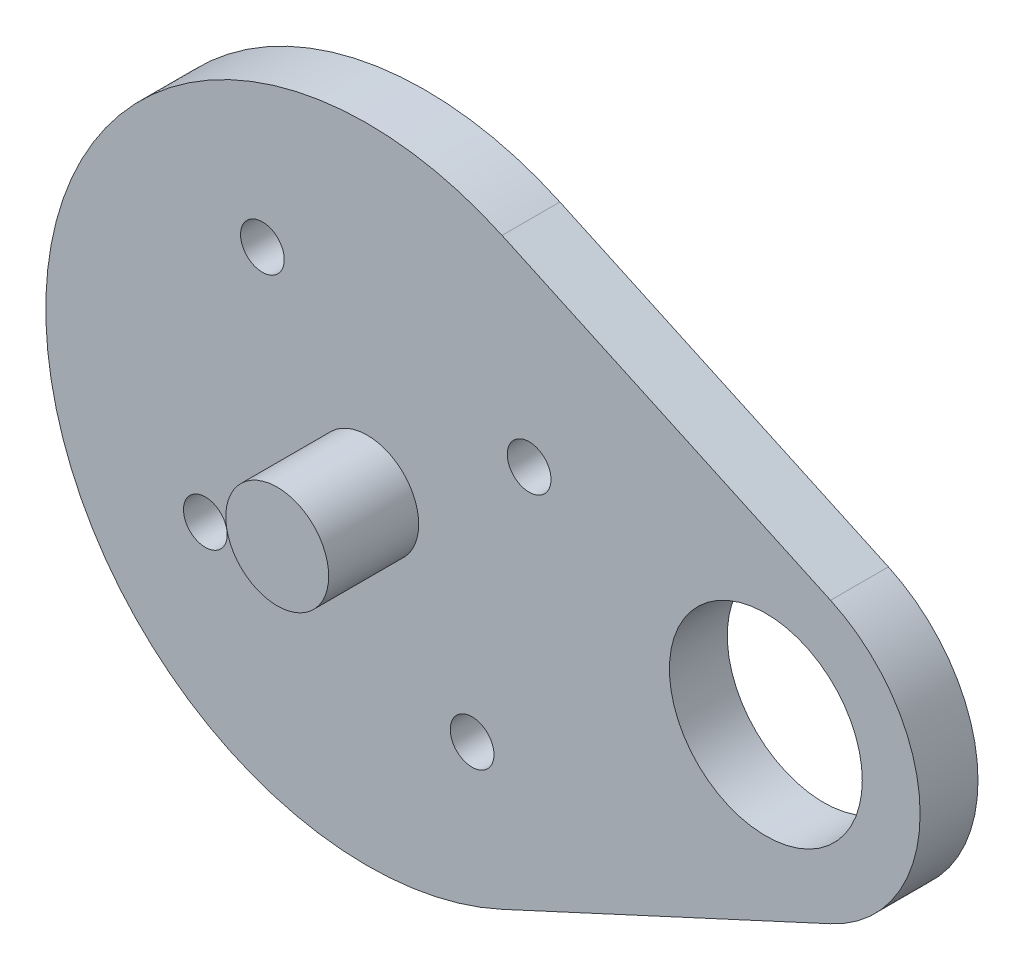
SolidWorks part; units mm, degrees
ref_plane "Front Plane" through (0, 0, 0) normal (0, 0, 1) x (1, 0, 0)
ref_plane "Top Plane" through (0, 0, 0) normal (0, 1, 0) x (1, 0, 0)
ref_plane "Right Plane" through (0, 0, 0) normal (1, 0, 0) x (0, 0, -1)
sketch "Sketch1" plane through (0, 0, 0) normal (0, 0, 1) x (1, 0, 0)
  line L0 (10.4839, 22.6956) -> (36.0323, 10.8939)
  line L1 (36.0323, -10.8939) -> (10.4839, -22.6956)
  circle A0 centre (0, 0) radius 22.215 construction
  circle A1 centre (31, 0) radius 10.2 construction
  arc A2 (10.4839, 22.6956) -> (10.4839, -22.6956) centre (0, 0) ccw
  arc A3 (36.0323, -10.8939) -> (36.0323, 10.8939) centre (31, 0) ccw
  dimension "D1" = 20.4
  dimension "D2" = 44.43
  dimension "D4" = 25
  dimension "D5" = 12
  dimension "D3" = 31
extrude "Boss-Extrude1" add sketch "Sketch1" along normal blind 4.5
sketch "Sketch2" plane through (0, 0, 4.5) normal (0, 0, 1) x (1, 0, 0)
  circle A0 centre (31, 0) radius 7.5
  dimension "D1" = 15
extrude "Cut-Extrude1" cut sketch "Sketch2" against normal through all
sketch "Sketch3" plane through (0, 0, 4.5) normal (0, 0, 1) x (1, 0, 0)
  circle A0 centre (0, 0) radius 4
  dimension "D1" = 8
extrude "Boss-Extrude2" add sketch "Sketch3" along normal blind 7
sketch "Sketch4" plane through (0, 0, 0) normal (0, 0, -1) x (-1, 0, 0)
  line L0 (-36.0323, 10.8939) -> (-56.0323, 10.8939)
  line L1 (-36.0323, -10.8939) -> (-56.0323, -10.8939)
  line L2 (-56.0323, -10.8939) -> (-56.0323, 10.8939)
  line L3 (22.5016, 10.8939) -> (42.5016, 10.8939)
  line L4 (42.5016, 10.8939) -> (42.5016, -10.8939)
  line L5 (42.5016, -10.8939) -> (22.5016, -10.8939)
  arc A0 (-10.4839, -22.6956) -> (-10.4839, 22.6956) centre (0, 0) ccw construction
  arc A1 (22.5016, -10.8939) -> (22.5016, 10.8939) centre (0, 0) ccw
  arc A2 (-36.0323, 10.8939) -> (-36.0323, -10.8939) centre (-31, 0) ccw construction
  arc A3 (-36.0323, 10.8939) -> (-36.0323, -10.8939) centre (-31, 0) ccw
  dimension "D1" = 20
  dimension "D2" = 20
extrude "Boss-Extrude3" add sketch "Sketch4" against normal up to surface (4.5 mm away) up to face at (4, 0, 4.5)
fillet "Fillet1" radius 10 4 edges at (-42.5016, 10.8939, 2.25) (-42.5016, -10.8939, 2.25) (56.0323, -10.8939, 2.25) (56.0323, 10.8939, 2.25)
sketch "Sketch6" plane through (0, 0, 0) normal (0, 0, -1) x (-1, 0, 0)
  line L0 (32.5016, -7.3844) -> (32.5016, 7.3844) construction
  line L2 (42.5016, 0) -> (-56.0323, 0) construction
  line L3 (32.5016, 7.3844) -> (38.7752, 0) construction
  line L4 (38.7752, 0) -> (32.5016, -7.3844) construction
  line L5 (-46.0323, -10.8939) -> (-46.0323, 10.8939) construction
  line L6 (32.5016, -7.3844) -> (-48.7204, -7.3844) construction
  line L7 (32.5016, 7.3844) -> (-48.7204, 7.3844) construction
  line L8 (42.5016, -0.8939) -> (42.5016, 0.8939) construction
  line L9 (-56.0323, 0.8939) -> (-56.0323, -0.8939) construction
  line L10 (41.7762, 16.9611) -> (41.8868, 17.0874) construction
  circle A2 centre (32.5016, -7.3844) radius 1
  circle A3 centre (32.5016, 7.3844) radius 1
  circle A4 centre (-46.0323, -7.3844) radius 1
  circle A5 centre (-46.0323, 7.3844) radius 1
  point P5 (32.5016, 0)
  point P16 (-46.0323, 7.3844)
  point P20 (-46.0323, -7.3844)
  dimension "D1" = 2
extrude "Cut-Extrude2" cut sketch "Sketch6" against normal through all
sketch "Sketch7" plane through (0, 0, 0) normal (0, 0, -1) x (-1, 0, 0)
  line L1 (-46.0408, 9.6361) -> (-47.9865, 8.5028)
  line L2 (-47.9865, 8.5028) -> (-47.978, 6.2512)
  line L3 (-47.978, 6.2512) -> (-46.0237, 5.1328)
  line L4 (-46.0237, 5.1328) -> (-44.078, 6.266)
  line L5 (-44.078, 6.266) -> (-44.0866, 8.5176)
  line L6 (-44.0866, 8.5176) -> (-46.0408, 9.6361)
  line L7 (-46.0408, -5.1328) -> (-47.9865, -6.266)
  line L8 (-47.9865, -6.266) -> (-47.978, -8.5176)
  line L9 (-47.978, -8.5176) -> (-46.0237, -9.6361)
  line L10 (-46.0237, -9.6361) -> (-44.078, -8.5028)
  line L11 (-44.078, -8.5028) -> (-44.0866, -6.2512)
  line L12 (-44.0866, -6.2512) -> (-46.0408, -5.1328)
  line L13 (32.5009, 9.6361) -> (30.5512, 8.5096)
  line L14 (30.5512, 8.5096) -> (30.552, 6.2579)
  line L15 (30.552, 6.2579) -> (32.5024, 5.1327)
  line L16 (32.5024, 5.1327) -> (34.452, 6.2593)
  line L17 (34.452, 6.2593) -> (34.4512, 8.5109)
  line L18 (34.4512, 8.5109) -> (32.5009, 9.6361)
  line L19 (32.5009, -5.1327) -> (30.5512, -6.2593)
  line L20 (30.5512, -6.2593) -> (30.552, -8.5109)
  line L21 (30.552, -8.5109) -> (32.5024, -9.6361)
  line L22 (32.5024, -9.6361) -> (34.452, -8.5096)
  line L23 (34.452, -8.5096) -> (34.4512, -6.2579)
  line L24 (34.4512, -6.2579) -> (32.5009, -5.1327)
  circle A0 centre (-46.0323, 7.3844) radius 1.95 construction
  circle A1 centre (-46.0323, -7.3844) radius 1.95 construction
  circle A2 centre (32.5016, 7.3844) radius 1.95 construction
  circle A3 centre (32.5016, -7.3844) radius 1.95 construction
  dimension "D1" = 2.2517
extrude "Cut-Extrude3" cut sketch "Sketch7" against normal blind 3
sketch "Sketch8" plane through (0, 0, 4.5) normal (0, 0, 1) x (1, 0, 0)
  line L0 (56.0323, 0.8939) -> (56.0323, -0.8939) construction
  line L2 (56.0323, 0.8939) -> (56.0323, -0.8939)
  line L3 (55.4014, -4.3896) -> (55.4014, 4.3896)
  line L4 (-42.5016, -0.8939) -> (-42.5016, 0.8939) construction
  line L6 (-42.5016, -0.8939) -> (-42.5016, 0.8939)
  line L7 (-41.8707, 4.3896) -> (-41.8707, -4.3896)
  arc A0 (56.0323, 0.8939) -> (46.0323, 10.8939) centre (46.0323, 0.8939) ccw construction
  arc A1 (46.0323, -10.8939) -> (56.0323, -0.8939) centre (46.0323, -0.8939) ccw construction
  arc A2 (56.0323, 0.8939) -> (55.4014, 4.3896) centre (46.0323, 0.8939) ccw
  arc A3 (55.4014, -4.3896) -> (56.0323, -0.8939) centre (46.0323, -0.8939) ccw
  arc A4 (-32.5016, 10.8939) -> (-42.5016, 0.8939) centre (-32.5016, 0.8939) ccw construction
  arc A5 (-42.5016, -0.8939) -> (-32.5016, -10.8939) centre (-32.5016, -0.8939) ccw construction
  arc A6 (-41.8707, 4.3896) -> (-42.5016, 0.8939) centre (-32.5016, 0.8939) ccw
  arc A7 (-42.5016, -0.8939) -> (-41.8707, -4.3896) centre (-32.5016, -0.8939) ccw
extrude "Cut-Extrude4" cut sketch "Sketch8" against normal through all
sketch "Sketch9" plane through (0, 0, 4.5) normal (0, 0, 1) x (1, 0, 0)
  circle A0 centre (0, 0) radius 15 construction
  circle A1 centre (-8.1543, 12.59) radius 1
  circle A2 centre (12.59, 8.1543) radius 1
  circle A3 centre (8.1543, -12.59) radius 1
  circle A4 centre (-12.59, -8.1543) radius 1
  point P14 (0, 0)
  dimension "D1" = 30
  dimension "D2" = 2
  dimension "D3" = 4
extrude "Cut-Extrude5" cut sketch "Sketch9" against normal through all
sketch "Sketch10" plane through (0, 0, 4.5) normal (0, 0, 1) x (1, 0, 0)
  circle A0 centre (-8.1543, 12.59) radius 1.7
  circle A1 centre (12.59, 8.1543) radius 1.7
  circle A2 centre (8.1543, -12.59) radius 1.7
  circle A3 centre (-12.59, -8.1543) radius 1.7
  dimension "D1" = 3.4
extrude "Cut-Extrude6" cut sketch "Sketch10" against normal blind 2.4
sketch "Sketch12" plane through (0, 0, 4.5) normal (0, 0, 1) x (1, 0, 0)
  line L0 (36.0323, 10.8939) -> (57.9117, 29.249)
  line L1 (57.9117, 29.249) -> (69.313, 0)
  line L2 (69.313, 0) -> (54.788, -25.8834)
  line L3 (54.788, -25.8834) -> (36.0323, -10.8939)
  line L4 (-22.5016, 10.8939) -> (-48.4564, 16.5716)
  line L5 (-48.4564, 16.5716) -> (-48.4564, -3.508)
  line L6 (-48.4564, -3.508) -> (-33.5552, -20.9456)
  line L7 (-33.5552, -20.9456) -> (-22.5016, -10.8939)
  arc A0 (-22.5016, 10.8939) -> (-22.5016, -10.8939) centre (0, 0) ccw
  arc A2 (36.0323, -10.8939) -> (36.0323, 10.8939) centre (31, 0) ccw
extrude "Cut-Extrude12" cut sketch "Sketch12" against normal through all
